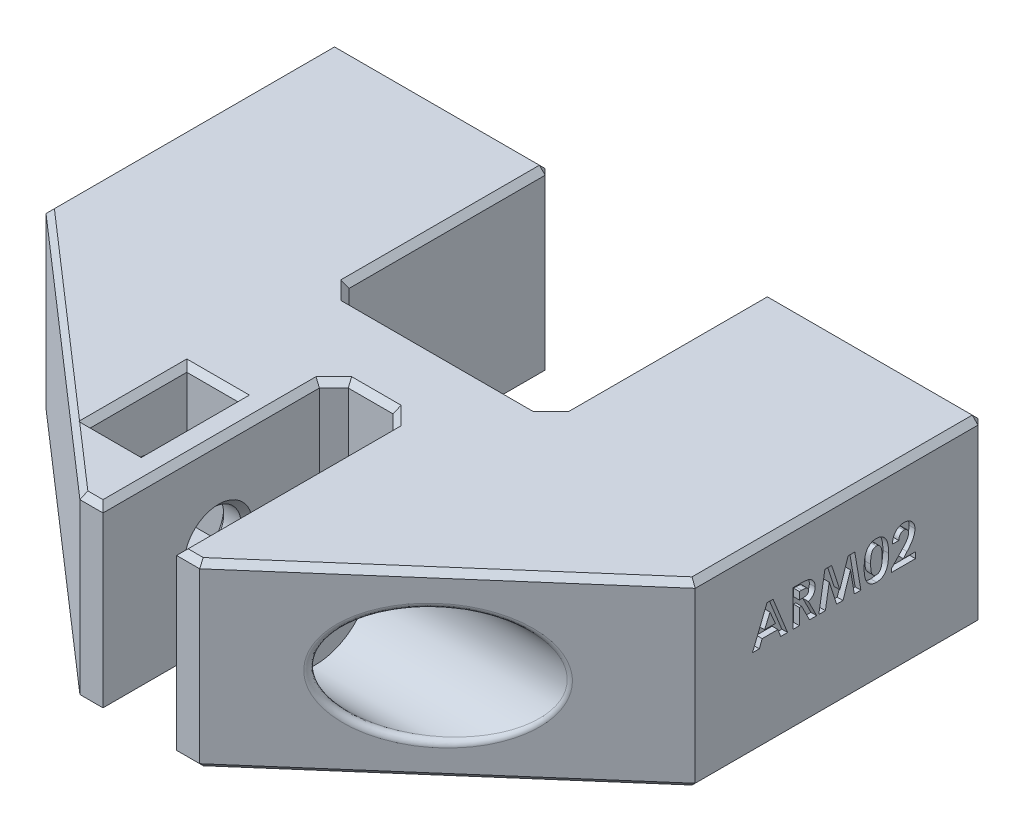
SolidWorks part; units mm, degrees
material "PET"
ref_plane "Front Plane" through (0, 0, 0) normal (0, 0, 1) x (1, 0, 0)
ref_plane "Top Plane" through (0, 0, 0) normal (0, 1, 0) x (1, 0, 0)
ref_plane "Right Plane" through (0, 0, 0) normal (1, 0, 0) x (0, 0, -1)
sketch "Sketch2" plane through (0, 0, 0) normal (0, 1, 0) x (1, 0, 0)
  line L0 (-3.2385, 0) -> (3.2385, 0)
  line L1 (0, 0) -> (0, 49.5) construction
  line L2 (3.2385, 0) -> (3.2385, -20.32)
  line L3 (3.2385, -20.32) -> (5.2705, -20.32)
  line L4 (5.2705, -20.32) -> (28.575, 0)
  line L5 (28.575, 0) -> (28.575, 25.4)
  line L6 (28.575, 25.4) -> (9.525, 25.4)
  line L7 (9.525, 25.4) -> (9.525, 6.35)
  line L8 (9.525, 6.35) -> (-9.525, 6.35)
  line L9 (-9.525, 25.4) -> (-9.525, 6.35)
  line L10 (-28.575, 25.4) -> (-9.525, 25.4)
  line L11 (-28.575, 0) -> (-28.575, 25.4)
  line L12 (-5.2705, -20.32) -> (-28.575, 0)
  line L13 (-3.2385, -20.32) -> (-5.2705, -20.32)
  line L14 (-3.2385, 0) -> (-3.2385, -20.32)
  point P4 (0, 0)
  point P13 (0, 6.35)
  dimension "D1" = 6.477
  dimension "D2" = 2.032
  dimension "D3" = 20.32
  dimension "D4" = 19.05
  dimension "D5" = 57.15
  dimension "D6" = 25.4
  dimension "D7" = 6.35
extrude "Boss-Extrude1" add sketch "Sketch2" along normal blind 15.875
sketch "Sketch6" plane through (0, 0, 0) normal (1, 0, 0) x (0, 0, -1)
  line L0 (-20.32, 15.875) -> (0, 15.875) construction
  line L1 (-20.32, 15.875) -> (-20.32, 0) construction
  circle A0 centre (-10.16, 7.9375) radius 2.5
  point P4 (-10.16, 15.875)
  point P8 (-20.32, 7.9375)
  dimension "D1" = 5
extrude "Cut-Extrude1" cut sketch "Sketch6" along normal up to surface (28.575 mm away) and the other way blind 12.7 up to face at (28.575, 7.9375, -12.7)
sketch "Sketch7" plane through (28.575, 0, 0) normal (1, 0, 0) x (0, 0, -1)
  circle A0 centre (-10.16, 7.9375) radius 5
  dimension "D1" = 10
extrude "Cut-Extrude2" cut sketch "Sketch7" against normal up to vertex (23.3045 mm away) up to point (5.2705, 0, 20.32)
sketch "Sketch15" plane through (0, 15.875, 0) normal (0, 1, 0) x (1, 0, 0)
  line L0 (0, -10.16) -> (-11.557, -10.16) construction
  line L1 (0, -12.66) -> (0, -7.66) construction
  line L2 (-3.2385, -20.32) -> (-3.2385, 0) construction
  line L3 (-5.7785, -5.9055) -> (-10.2743, -5.9055)
  line L4 (-5.7785, -5.9055) -> (-5.7785, -14.4145)
  line L5 (-5.7785, -14.4145) -> (-10.2743, -14.4145)
  line L6 (-10.2743, -5.9055) -> (-10.2743, -14.4145)
  point P8 (-5.7785, -10.16)
  dimension "D1" = 4.4958
  dimension "D2" = 8.509
  dimension "D3" = 2.54
extrude "Cut-Extrude6" cut sketch "Sketch15" against normal blind 11.938
hole_wizard "M5x0.8 Tapped Hole1" positions "Sketch8" profile "Sketch9" tap size "M5x0.8" standard "ANSI Metric"
sketch "Sketch8" plane through (0, 0, -25.4) normal (0, 0, -1) x (-1, 0, 0)
  line L0 (-28.575, 15.875) -> (-28.575, 0) construction
  line L1 (-28.575, 15.875) -> (-9.525, 15.875) construction
  line L2 (28.575, 15.875) -> (28.575, 0) construction
  line L3 (9.525, 15.875) -> (28.575, 15.875) construction
  point P0 (-19.05, 7.9375)
  point P2 (19.05, 7.9375)
  point P7 (-28.575, 7.9375)
  point P10 (-19.05, 15.875)
  point P13 (28.575, 7.9375)
  point P16 (19.05, 15.875)
sketch "Sketch9" plane through (19.05, 7.9375, -25.4) normal (1, 0, 0) x (0, 1, 0)
  line L0 (0, 0) -> (0, 22.225)
  line L1 (0, 22.225) -> (2.5, 22.225)
  line L2 (2.5, 22.225) -> (2.5, 0)
  line L5 (2.5, 0) -> (0, 0)
  line L10 (0, 22.225) -> (-2.5, 22.225) construction
  line L11 (0, -6.35) -> (0, 107.95) construction
  dimension "Tap Drill Dia." = 5
  dimension "Tap Drill Depth" = 22.225
  dimension "Drill Angle" = 180
cosmetic thread "Hole Thread1" parameters "D1"=10.0076, "D2"=5
cosmetic thread "Hole Thread2" parameters "D1"=10.0076, "D2"=5
chamfer "Chamfer2" distance 1.27 angle 45 4 edges at (9.525, 7.9375, -6.35) (-9.525, 7.9375, -6.35) (3.2385, 7.9375, 0) (-3.2385, 7.9375, 0)
chamfer "Chamfer1" distance 0.508 angle 45 51 edges at (-3.2385, 0, 10.795) (0, 0, 0) (3.2385, 0, 10.795) (3.2385, 15.875, 10.795) (0, 15.875, 0) (-3.2385, 15.875, 10.795) (28.575, 7.9375, -25.4) (-9.525, 15.875, -16.51) (0, 15.875, -6.35) (9.525, 15.875, -16.51) (16.9228, 0, 10.16) (28.575, 0, -12.7) (19.05, 0, -25.4) (-19.05, 0, -25.4) (-16.9228, 0, 10.16) (-28.575, 0, -12.7) (-28.575, 7.9375, -25.4) (-16.9228, 15.875, 10.16) (-28.575, 15.875, -12.7) (-19.05, 15.875, -25.4) (-9.525, 7.9375, -25.4) (-9.525, 0, -16.51) (0, 0, -6.35) (9.525, 0, -16.51) (9.525, 7.9375, -25.4) (19.05, 15.875, -25.4) (28.575, 15.875, -12.7) (16.9228, 15.875, 10.16) (-4.2545, 0, 20.32) (4.2545, 0, 20.32) (-4.2545, 15.875, 20.32) (4.2545, 15.875, 20.32) (2.6035, 15.875, 0.635) (-2.6035, 15.875, 0.635) (-8.89, 15.875, -6.985) (8.89, 15.875, -6.985) (-8.89, 0, -6.985) (-2.6035, 0, 0.635) (2.6035, 0, 0.635) (8.89, 0, -6.985) (-8.0264, 15.875, 5.9055) (-10.2743, 15.875, 10.16) (-8.0264, 15.875, 14.4145) (-5.7785, 15.875, 10.16) (-21.55, 7.9375, -25.4) (16.55, 7.9375, -25.4) (5.2705, 7.9375, 7.66) (3.2385, 7.9375, 7.66) (-5.7785, 7.9375, 7.66) (-10.2743, 7.9375, 12.66) (-3.2385, 7.9375, 12.66)
sketch "Sketch11" plane through (28.575, 0, 0) normal (1, 0, 0) x (0, 0, -1)
  line L0 (0, 7.9375) -> (24.892, 7.9375) construction
  line L1 (0, 15.367) -> (0, 0.508) construction
  line L2 (24.892, 0.508) -> (24.892, 15.367) construction
  text T0 "<b>ARM02</b>"
extrude "Cut-Extrude4" cut sketch "Sketch11" against normal blind 0.508
sketch "Sketch12" plane through (-28.575, 0, 0) normal (-1, 0, 0) x (0, 0, 1)
  line L0 (-24.892, 7.9375) -> (0, 7.9375) construction
  line L1 (-24.892, 15.367) -> (-24.892, 0.508) construction
  line L2 (0, 15.367) -> (0, 0.508) construction
  text T0 "<b>ARM02</b>"
extrude "Cut-Extrude5" cut sketch "Sketch12" against normal blind 0.508
fillet "Fillet1" radius 0.508 1 edges at (22.6571, 7.9375, 5.16)
